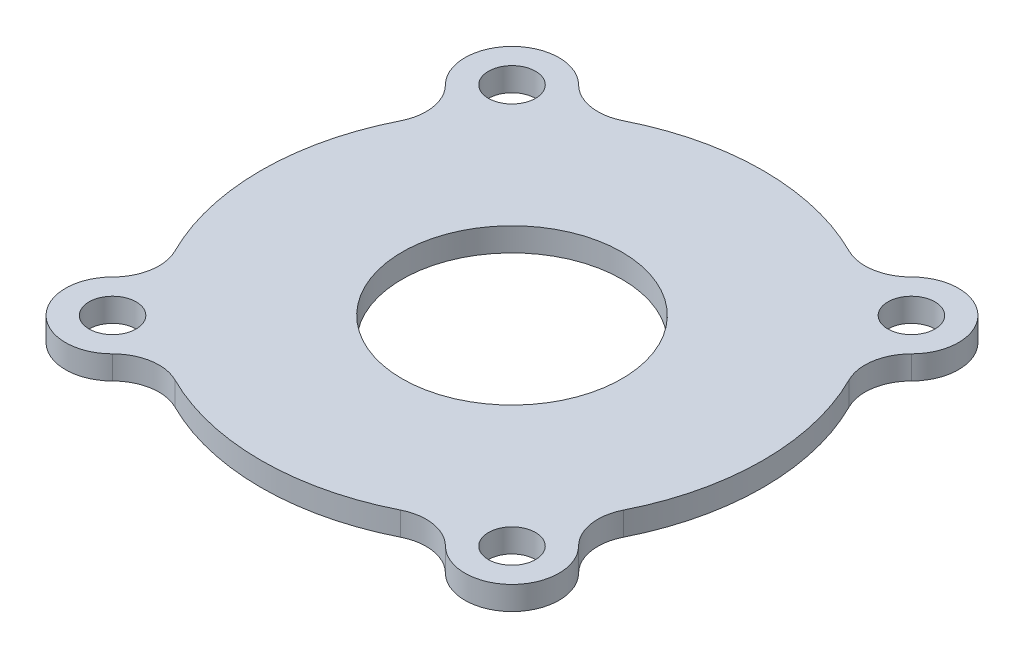
SolidWorks part; units mm, degrees
ref_plane "Front Plane" through (0, 0, 0) normal (0, 0, 1) x (1, 0, 0)
ref_plane "Top Plane" through (0, 0, 0) normal (0, 1, 0) x (1, 0, 0)
ref_plane "Right Plane" through (0, 0, 0) normal (1, 0, 0) x (0, 0, -1)
sketch "Sketch1" plane through (0, 0, 0) normal (0, 1, 0) x (1, 0, 0)
  line L0 (0, 0) -> (12.7279, 0) construction
  line L1 (12.7279, 12.7279) -> (25.4558, 0) construction
  line L2 (12.7279, 12.7279) -> (0, 0) construction
  arc A0 (14.8492, 10.6066) -> (14.297, 7.1829) centre (16.9434, 8.5125) ccw
  arc A2 (10.6066, 14.8492) -> (7.1829, 14.297) centre (8.5125, 16.9434) cw
  arc A3 (10.6066, -14.8492) -> (7.1829, -14.297) centre (8.5125, -16.9434) ccw
  arc A4 (14.8492, -10.6066) -> (14.297, -7.1829) centre (16.9434, -8.5125) cw
  arc A5 (-14.8492, -10.6066) -> (-14.297, -7.1829) centre (-16.9434, -8.5125) ccw
  arc A6 (-10.6066, -14.8492) -> (-7.1829, -14.297) centre (-8.5125, -16.9434) cw
  arc A7 (-10.6066, 14.8492) -> (-7.1829, 14.297) centre (-8.5125, 16.9434) ccw
  arc A8 (-14.8492, 10.6066) -> (-14.297, 7.1829) centre (-16.9434, 8.5125) cw
  point P8 (21.4687, -23.3981)
  point P11 (0, 0)
  point P32 (0, 0)
  circle B0 centre (0, 0) radius 7
  circle B1 centre (0, 0) radius 11
  circle B2 centre (0, 0) radius 13
  circle B3 centre (0, 0) radius 16
  circle B4 centre (12.7279, 12.7279) radius 1.5
  arc B5 (9.728, 12.703) -> (12.703, 9.728) centre (12.7279, 12.7279) cw
  arc B6 (12.703, -9.728) -> (9.728, -12.703) centre (12.7279, -12.7279) cw
  circle B7 centre (12.7279, -12.7279) radius 1.5
  arc B8 (-9.728, -12.703) -> (-12.703, -9.728) centre (-12.7279, -12.7279) cw
  circle B9 centre (-12.7279, -12.7279) radius 1.5
  arc B10 (-12.703, 9.728) -> (-9.728, 12.703) centre (-12.7279, 12.7279) cw
  circle B11 centre (-12.7279, 12.7279) radius 1.5
  dimension "D1" = 45
  dimension "D2" = 18
  dimension "D3" = 4
sketch_block_instance "Block1-1"
sketch_block "Block1" parameters "D2"=12, "D1"=18
extrude "Boss-Extrude1" add sketch "Sketch1" along normal blind 1.5 contours B2 B1 | B3 B2 | B1 B0 | B5 B3 B4 | B10 B3 B11 | B8 B3 B9 | B6 B3 B7 | A0 B5 B3 | B3 B5 A2 | A3 B6 B3 | B3 B6 A4 | B3 B8 A6 | A5 B8 B3 | A7 B10 B3 | B3 B10 A8 region at (13.8323, 0, -10.0301) region at (13.6886, 0, -9.2281) region at (15.1281, 0, -3.5866) region at (9.2281, 0, -13.6886) region at (13.6886, 0, 9.2281) region at (-9.2281, 0, -13.6886) region at (14.7892, 0, 14.7892) region at (-10.0301, 0, -13.8323) region at (9.2281, 0, 13.6886) region at (-13.6886, 0, -9.2281) region at (-9.2281, 0, 13.6886) region at (-13.6886, 0, 9.2281) region at (-14.7892, 0, 14.7892) region at (-10.6889, 0, 0) region at (-12.6323, 0, 0)
extrude "Boss-Extrude2" add sketch "Sketch1<3>" against normal blind 1 contours B2 B1 region at (-12.6323, 0, 0)
sketch "Sketch1<3>" plane through (0, 0, 0) normal (0, 1, 0) x (1, 0, 0) same geometry as "Sketch1"
